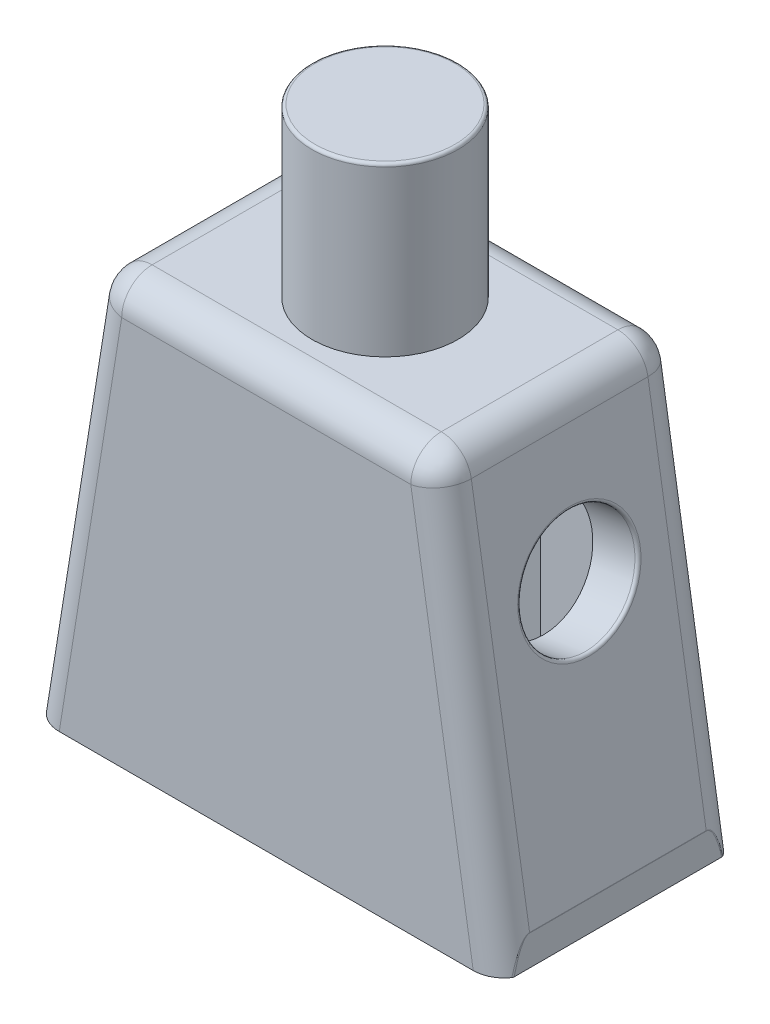
SolidWorks part; units mm, degrees
ref_plane "Front Plane" through (0, 0, 0) normal (0, 0, 1) x (1, 0, 0)
ref_plane "Top Plane" through (0, 0, 0) normal (0, 1, 0) x (1, 0, 0)
ref_plane "Right Plane" through (0, 0, 0) normal (1, 0, 0) x (0, 0, -1)
sketch "Sketch1" plane through (0, 0, 0) normal (0, 0, 1) x (1, 0, 0)
  line L0 (0, 0) -> (0, 13.8) construction
  line L1 (7.65, 0) -> (-7.65, 0)
  line L2 (-7.65, 0) -> (-7.65, 1)
  line L3 (-7.65, 1) -> (-5.6, 13.8)
  line L4 (-5.6, 13.8) -> (5.6, 13.8)
  line L5 (7.65, 1) -> (5.6, 13.8)
  line L6 (7.65, 0) -> (7.65, 1)
  dimension "D1" = 13.8
  dimension "D2" = 1
  dimension "D3" = 7.65
  dimension "D4" = 11.2
extrude "Torso" add sketch "Sketch1" along normal mid plane 7.8
shell "Shell1" thickness 1.5 removed face at (0, 0, 0)
sketch "Sketch2" plane through (7.6148, 1.2196, 0) normal (0.9874, 0.1581, 0) x (0, 0, -1)
  line L0 (0, 12.7408) -> (0, 0) construction
  line L1 (-3.9, 12.7408) -> (3.9, 12.7408) construction
  circle A0 centre (0, 7.7902) radius 1.9
  dimension "D1" = 3.8
  dimension "D2" = 9
extrude "Arm Hole" cut sketch "Sketch2" against normal up to next
mirror "Mirror1" about plane through (0, 0, 0) normal (1, 0, 0) of "Arm Hole"
sketch "Sketch3" plane through (0, 0, 0) normal (0, -1, 0) x (1, 0, 0)
  line L0 (0, 3.9) -> (0, 0) construction
  line L1 (-7.65, 3.9) -> (7.65, 3.9) construction
  line L2 (0, 0) -> (0, -3.9) construction
  line L3 (-7.65, -3.9) -> (7.65, -3.9) construction
  line L4 (-2.7, 2.4) -> (-1.5, 2.4)
  line L5 (4.3211, 2.4) -> (-4.3211, 2.4) construction
  line L6 (-1.5, 2.4) -> (-1.5, 1.6)
  line L7 (-1.5, 1.6) -> (-2.7, 2.4)
  line L8 (1.5, 1.6) -> (2.7, 2.4)
  line L9 (1.5, 2.4) -> (1.5, 1.6)
  line L10 (2.7, 2.4) -> (1.5, 2.4)
  dimension "D1" = 3
  dimension "D2" = 1.2
  dimension "D3" = 0.8
extrude "Hip Ribs" add sketch "Sketch3" against normal up to next
mirror "Mirror2" about plane through (0, 0, 0) normal (0, 0, 1) of "Hip Ribs"
sketch "Sketch4" plane through (0, 13.8, 0) normal (0, 1, 0) x (1, 0, 0)
  circle A0 centre (0, 0) radius 2.4
  dimension "D1" = 4.8
extrude "Neck" add sketch "Sketch4" along normal blind 5.5
sketch "Sketch5" plane through (0, 12.3, 0) normal (0, -1, 0) x (1, 0, 0)
  circle A0 centre (0, 0) radius 1.25
  dimension "D1" = 2.5
extrude "Inner Neck Cut" cut sketch "Sketch5" against normal blind 4.25
fillet "Fillet1" radius 1 4 edges at (-6.625, 7.4, 3.9) (-6.625, 7.4, -3.9) (6.625, 7.4, -3.9) (6.625, 7.4, 3.9)
fillet "Fillet2" radius 1 8 edges at (5.3034, 13.8, 3.6071) (5.6, 13.8, 0) (5.3034, 13.8, -3.6071) (0, 13.8, -3.9) (-5.3034, 13.8, -3.6071) (-5.6, 13.8, 0) (-5.3034, 13.8, 3.6071) (0, 13.8, 3.9)
fillet "Fillet3" radius 0.1 9 edges at (7.65, 0.7449, 3.1812) (7.65, 0.7449, -3.1812) (-7.65, 0.7449, 3.1812) (-7.65, 0.7449, -3.1812) (7.65, 1, 0) (-7.65, 1, 0) (-2.4, 19.3, 0) (-6.0824, 10.7878, 0) (6.0824, 10.7878, 0)
